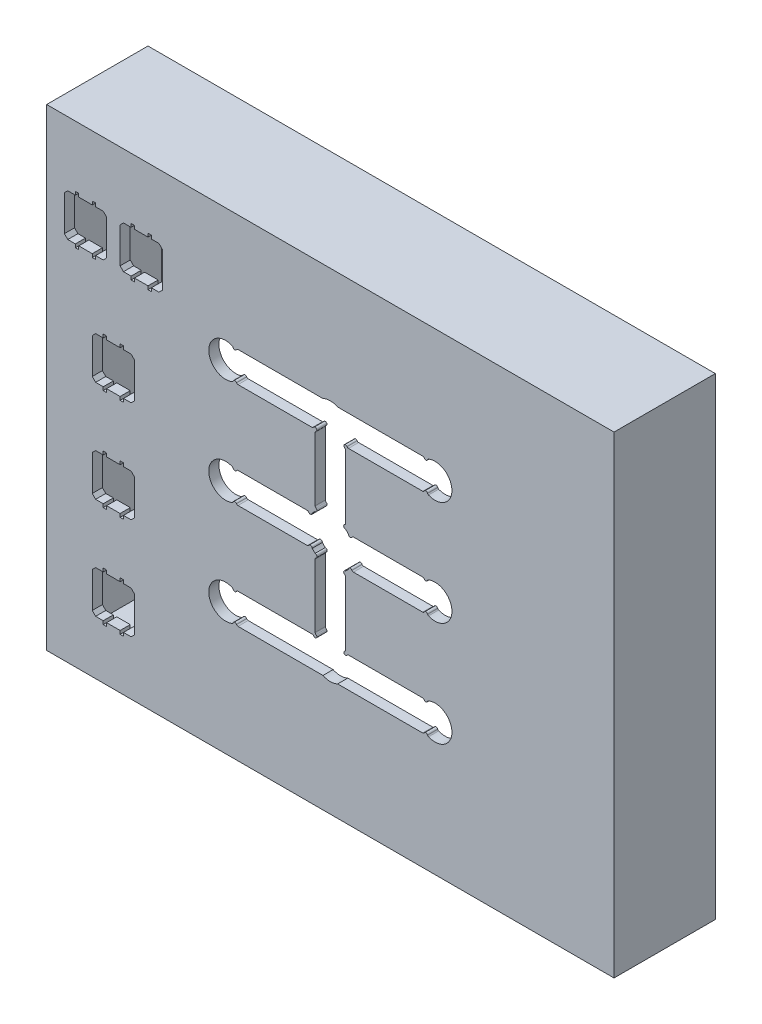
SolidWorks part; units mm, degrees
ref_plane "정면" through (0, 0, 0) normal (0, 0, 1) x (1, 0, 0)
ref_plane "윗면" through (0, 0, 0) normal (0, 1, 0) x (1, 0, 0)
ref_plane "우측면" through (0, 0, 0) normal (1, 0, 0) x (0, 0, -1)
sketch "스케치1" plane through (0, 0, 0) normal (0, 0, 1) x (1, 0, 0)
  line L1 (84, -70) -> (-84, -70)
  line L2 (84, -70) -> (84, 70)
  line L3 (84, 70) -> (-84, 70)
  line L4 (-84, -70) -> (-84, 70)
  line L5 (84, -70) -> (-84, 70) construction
  line L6 (84, 70) -> (-84, -70) construction
  point P0 (0, 0)
  dimension "D1" = 168
  dimension "D2" = 140
extrude "보스-돌출1" add sketch "스케치1" along normal blind 3
sketch "스케치3" plane through (0, 0, 0) normal (0, 0, -1) x (-1, 0, 0)
  line L1 (84, -70) -> (-84, -70)
  line L2 (84, -70) -> (84, 70)
  line L3 (84, 70) -> (-84, 70)
  line L4 (-84, -70) -> (-84, 70)
  line L5 (84, -70) -> (-84, 70) construction
  line L6 (84, 70) -> (-84, -70) construction
  point P0 (0, 0)
extrude "돌출-얇게3" add sketch "스케치3" along normal blind 27 thin
sketch "스케치11" plane through (0, 0, 3) normal (0, 0, 1) x (1, 0, 0)
  line L0 (58, 70) -> (58, -70) construction
  line L1 (84, 70) -> (-84, 70) construction
  line L2 (-84, -70) -> (84, -70) construction
  line L3 (84, -70) -> (84, 70) construction
  line L4 (64.25, -41.5) -> (64.25, -54) construction
  line L5 (58, -41.5) -> (70.5, -41.5)
  line L6 (58, -41.5) -> (58, -54)
  line L7 (58, -54) -> (70.5, -54)
  line L8 (70.5, -41.5) -> (70.5, -54)
  line L9 (61.25, -40.5) -> (62.25, -40.5)
  line L10 (61.25, -40.5) -> (61.25, -41.5)
  line L11 (61.25, -41.5) -> (62.25, -41.5)
  line L12 (62.25, -40.5) -> (62.25, -41.5)
  line L13 (64.25, -54) -> (64.25, -47.75) construction
  line L14 (64.25, -47.75) -> (70.5, -47.75) construction
  line L15 (67.25, -41.5) -> (66.25, -41.5)
  line L16 (66.25, -40.5) -> (66.25, -41.5)
  line L17 (67.25, -40.5) -> (66.25, -40.5)
  line L18 (67.25, -40.5) -> (67.25, -41.5)
  line L19 (61.25, -54) -> (62.25, -54)
  line L20 (62.25, -55) -> (62.25, -54)
  line L21 (61.25, -55) -> (62.25, -55)
  line L22 (61.25, -55) -> (61.25, -54)
  line L23 (67.25, -55) -> (67.25, -54)
  line L24 (67.25, -55) -> (66.25, -55)
  line L25 (66.25, -55) -> (66.25, -54)
  line L26 (67.25, -54) -> (66.25, -54)
  line L27 (64.25, -47.75) -> (64.25, 62.7587) construction
  line L28 (58, -11.5) -> (58, -24)
  line L29 (58, -11.5) -> (70.5, -11.5)
  line L30 (70.5, -11.5) -> (70.5, -24)
  line L31 (58, -24) -> (70.5, -24)
  line L32 (61.25, -10.5) -> (61.25, -11.5)
  line L33 (61.25, -10.5) -> (62.25, -10.5)
  line L34 (62.25, -10.5) -> (62.25, -11.5)
  line L35 (61.25, -11.5) -> (62.25, -11.5)
  line L36 (67.25, -11.5) -> (66.25, -11.5)
  line L37 (66.25, -10.5) -> (66.25, -11.5)
  line L38 (67.25, -10.5) -> (66.25, -10.5)
  line L39 (67.25, -10.5) -> (67.25, -11.5)
  line L40 (67.25, -25) -> (67.25, -24)
  line L41 (67.25, -24) -> (66.25, -24)
  line L42 (66.25, -25) -> (66.25, -24)
  line L43 (67.25, -25) -> (66.25, -25)
  line L44 (61.25, -24) -> (62.25, -24)
  line L45 (62.25, -25) -> (62.25, -24)
  line L46 (61.25, -25) -> (62.25, -25)
  line L47 (61.25, -25) -> (61.25, -24)
  line L48 (58, 18.5) -> (58, 6)
  line L49 (58, 18.5) -> (70.5, 18.5)
  line L50 (70.5, 18.5) -> (70.5, 6)
  line L51 (58, 6) -> (70.5, 6)
  line L52 (61.25, 19.5) -> (61.25, 18.5)
  line L53 (61.25, 19.5) -> (62.25, 19.5)
  line L54 (62.25, 19.5) -> (62.25, 18.5)
  line L55 (61.25, 18.5) -> (62.25, 18.5)
  line L56 (67.25, 18.5) -> (66.25, 18.5)
  line L57 (66.25, 19.5) -> (66.25, 18.5)
  line L58 (67.25, 19.5) -> (66.25, 19.5)
  line L59 (67.25, 19.5) -> (67.25, 18.5)
  line L60 (67.25, 5) -> (67.25, 6)
  line L61 (67.25, 6) -> (66.25, 6)
  line L62 (66.25, 5) -> (66.25, 6)
  line L63 (67.25, 5) -> (66.25, 5)
  line L64 (61.25, 6) -> (62.25, 6)
  line L65 (62.25, 5) -> (62.25, 6)
  line L66 (61.25, 5) -> (62.25, 5)
  line L67 (61.25, 5) -> (61.25, 6)
  line L68 (72.5, 51) -> (72.5, 38.5) construction
  line L69 (66.25, 51) -> (78.75, 51)
  line L70 (66.25, 51) -> (66.25, 38.5)
  line L71 (66.25, 38.5) -> (78.75, 38.5)
  line L72 (78.75, 51) -> (78.75, 38.5)
  line L73 (70.5, 52) -> (69.5, 52)
  line L74 (70.5, 52) -> (70.5, 51)
  line L75 (70.5, 51) -> (69.5, 51)
  line L76 (69.5, 52) -> (69.5, 51)
  line L77 (72.5, 38.5) -> (72.5, 44.75) construction
  line L78 (72.5, 44.75) -> (78.75, 44.75) construction
  line L79 (74.5, 51) -> (75.5, 51)
  line L80 (75.5, 52) -> (75.5, 51)
  line L81 (74.5, 52) -> (75.5, 52)
  line L82 (74.5, 52) -> (74.5, 51)
  line L83 (74.5, 37.5) -> (74.5, 38.5)
  line L84 (74.5, 37.5) -> (75.5, 37.5)
  line L85 (75.5, 37.5) -> (75.5, 38.5)
  line L86 (74.5, 38.5) -> (75.5, 38.5)
  line L87 (70.5, 38.5) -> (69.5, 38.5)
  line L88 (69.5, 37.5) -> (69.5, 38.5)
  line L89 (70.5, 37.5) -> (69.5, 37.5)
  line L90 (70.5, 37.5) -> (70.5, 38.5)
  line L91 (54, 37.5) -> (53, 37.5)
  line L92 (53, 37.5) -> (53, 38.5)
  line L93 (54, 38.5) -> (53, 38.5)
  line L94 (54, 37.5) -> (54, 38.5)
  line L95 (58, 37.5) -> (58, 38.5)
  line L96 (58, 37.5) -> (59, 37.5)
  line L97 (59, 37.5) -> (59, 38.5)
  line L98 (58, 38.5) -> (59, 38.5)
  line L99 (62.25, 38.5) -> (49.75, 38.5)
  line L100 (49.75, 51) -> (49.75, 38.5)
  line L101 (62.25, 51) -> (49.75, 51)
  line L102 (62.25, 51) -> (62.25, 38.5)
  line L103 (58, 51) -> (59, 51)
  line L104 (59, 52) -> (59, 51)
  line L105 (58, 52) -> (59, 52)
  line L106 (58, 52) -> (58, 51)
  line L107 (54, 52) -> (54, 51)
  line L108 (54, 52) -> (53, 52)
  line L109 (53, 52) -> (53, 51)
  line L110 (54, 51) -> (53, 51)
  line L111 (-58, -70) -> (-58, 70) construction
  line L112 (-84, 70) -> (-84, -70) construction
  line L113 (-64.25, -70) -> (-64.25, 70) construction
  line L114 (-64.25, -47.75) -> (-76.7581, -47.75) construction
  line L115 (-70.5, -41.5) -> (-58, -41.5)
  line L116 (-70.5, -41.5) -> (-70.5, -54)
  line L117 (-70.5, -54) -> (-58, -54)
  line L118 (-58, -41.5) -> (-58, -54)
  line L119 (-70.5, -41.5) -> (-58, -54) construction
  line L120 (-70.5, -54) -> (-58, -41.5) construction
  line L121 (-58, -24) -> (-70.5, -24)
  line L122 (-58, -24) -> (-58, -11.5)
  line L123 (-58, -11.5) -> (-70.5, -11.5)
  line L124 (-70.5, -24) -> (-70.5, -11.5)
  line L125 (-58, 6) -> (-70.5, 6)
  line L126 (-58, 6) -> (-58, 18.5)
  line L127 (-58, 18.5) -> (-70.5, 18.5)
  line L128 (-70.5, 6) -> (-70.5, 18.5)
  line L129 (-66.25, 38.5) -> (-78.75, 38.5)
  line L130 (-66.25, 38.5) -> (-66.25, 51)
  line L131 (-66.25, 51) -> (-78.75, 51)
  line L132 (-78.75, 38.5) -> (-78.75, 51)
  line L137 (-62.25, 38.5) -> (-49.75, 38.5)
  line L138 (-62.25, 38.5) -> (-62.25, 51)
  line L139 (-62.25, 51) -> (-49.75, 51)
  line L140 (-49.75, 38.5) -> (-49.75, 51)
  line L141 (-64.25, -17.75) -> (-76.7581, -17.75) construction
  line L142 (-64.25, 12.25) -> (-76.7581, 12.25) construction
  line L143 (-49.75, 44.75) -> (-78.75, 44.75) construction
  line L144 (-56, 38.5) -> (-56, 51) construction
  line L145 (-72.5, 38.5) -> (-72.5, 51) construction
  line L146 (-67.25, -54) -> (-66.25, -54)
  line L147 (-61.25, -55) -> (-62.25, -55)
  line L148 (-61.25, -55) -> (-61.25, -54)
  line L149 (-61.25, -54) -> (-62.25, -54)
  line L150 (-62.25, -55) -> (-62.25, -54)
  line L151 (-66.25, -55) -> (-66.25, -54)
  line L152 (-67.25, -55) -> (-66.25, -55)
  line L153 (-67.25, -55) -> (-67.25, -54)
  line L154 (-61.25, -41.5) -> (-62.25, -41.5)
  line L155 (-62.25, -40.5) -> (-62.25, -41.5)
  line L156 (-61.25, -40.5) -> (-62.25, -40.5)
  line L157 (-61.25, -40.5) -> (-61.25, -41.5)
  line L158 (-67.25, -40.5) -> (-67.25, -41.5)
  line L159 (-67.25, -40.5) -> (-66.25, -40.5)
  line L160 (-66.25, -40.5) -> (-66.25, -41.5)
  line L161 (-67.25, -41.5) -> (-66.25, -41.5)
  line L162 (-66.25, -11.5) -> (-67.25, -11.5)
  line L163 (-61.25, -25) -> (-62.25, -25)
  line L164 (-61.25, -25) -> (-61.25, -24)
  line L165 (-61.25, -24) -> (-62.25, -24)
  line L166 (-62.25, -25) -> (-62.25, -24)
  line L167 (-66.25, -25) -> (-67.25, -25)
  line L168 (-66.25, -25) -> (-66.25, -24)
  line L169 (-66.25, -24) -> (-67.25, -24)
  line L170 (-67.25, -25) -> (-67.25, -24)
  line L171 (-67.25, -10.5) -> (-67.25, -11.5)
  line L172 (-66.25, -10.5) -> (-67.25, -10.5)
  line L173 (-66.25, -10.5) -> (-66.25, -11.5)
  line L174 (-61.25, -11.5) -> (-62.25, -11.5)
  line L175 (-62.25, -10.5) -> (-62.25, -11.5)
  line L176 (-61.25, -10.5) -> (-62.25, -10.5)
  line L177 (-61.25, -10.5) -> (-61.25, -11.5)
  line L178 (-61.25, 18.5) -> (-62.25, 18.5)
  line L179 (-61.25, 5) -> (-62.25, 5)
  line L180 (-61.25, 5) -> (-61.25, 6)
  line L181 (-61.25, 6) -> (-62.25, 6)
  line L182 (-62.25, 5) -> (-62.25, 6)
  line L183 (-66.25, 5) -> (-67.25, 5)
  line L184 (-66.25, 5) -> (-66.25, 6)
  line L185 (-66.25, 6) -> (-67.25, 6)
  line L186 (-67.25, 5) -> (-67.25, 6)
  line L187 (-62.25, 19.5) -> (-62.25, 18.5)
  line L188 (-61.25, 19.5) -> (-62.25, 19.5)
  line L189 (-61.25, 19.5) -> (-61.25, 18.5)
  line L190 (-66.25, 18.5) -> (-67.25, 18.5)
  line L191 (-67.25, 19.5) -> (-67.25, 18.5)
  line L192 (-66.25, 19.5) -> (-67.25, 19.5)
  line L193 (-66.25, 19.5) -> (-66.25, 18.5)
  line L194 (-59, 38.5) -> (-58, 38.5)
  line L195 (-53, 37.5) -> (-54, 37.5)
  line L196 (-53, 37.5) -> (-53, 38.5)
  line L197 (-53, 38.5) -> (-54, 38.5)
  line L198 (-54, 37.5) -> (-54, 38.5)
  line L199 (-70.5, 38.5) -> (-69.5, 38.5)
  line L200 (-70.5, 38.5) -> (-70.5, 37.5)
  line L201 (-70.5, 37.5) -> (-69.5, 37.5)
  line L202 (-69.5, 38.5) -> (-69.5, 37.5)
  line L203 (-58, 37.5) -> (-58, 38.5)
  line L204 (-59, 37.5) -> (-58, 37.5)
  line L205 (-59, 37.5) -> (-59, 38.5)
  line L206 (-59, 52) -> (-59, 51)
  line L207 (-59, 52) -> (-58, 52)
  line L208 (-58, 52) -> (-58, 51)
  line L209 (-59, 51) -> (-58, 51)
  line L210 (-53, 51) -> (-54, 51)
  line L211 (-54, 52) -> (-54, 51)
  line L212 (-53, 52) -> (-54, 52)
  line L213 (-53, 52) -> (-53, 51)
  line L214 (-74.5, 37.5) -> (-75.5, 37.5)
  line L215 (-75.5, 38.5) -> (-75.5, 37.5)
  line L216 (-74.5, 38.5) -> (-75.5, 38.5)
  line L217 (-74.5, 38.5) -> (-74.5, 37.5)
  line L218 (-74.5, 51) -> (-74.5, 52)
  line L219 (-74.5, 51) -> (-75.5, 51)
  line L220 (-75.5, 51) -> (-75.5, 52)
  line L221 (-74.5, 52) -> (-75.5, 52)
  line L222 (-70.5, 52) -> (-69.5, 52)
  line L223 (-69.5, 51) -> (-69.5, 52)
  line L224 (-70.5, 51) -> (-69.5, 51)
  line L225 (-70.5, 51) -> (-70.5, 52)
  point P24 (62.25, -41)
  point P90 (74.5, 51.5)
  point P125 (-64.25, -47.75)
  point P210 (-54, 38)
  point P215 (-70.5, 38)
  dimension "D1" = 26
  dimension "D2" = 12.5
  dimension "D3" = 12.5
  dimension "D4" = 1
  dimension "D5" = 1
  dimension "D6" = 4
  dimension "D7" = 16
  dimension "D9" = 12.5
  dimension "D10" = 12.5
  dimension "D11" = 1
  dimension "D12" = 1
  dimension "D13" = 4
  dimension "D14" = 2
  dimension "D15" = 19
  dimension "D16" = 26
  dimension "D17" = 6.25
  dimension "D18" = 12.5
  dimension "D19" = 12.5
  dimension "D20" = 2
  dimension "D21" = 2
  dimension "D22" = 1
  dimension "D23" = 2
  dimension "D24" = 2
  dimension "D25" = 1
  dimension "D26" = 1
  dimension "D27" = 2
  dimension "D8" = 3
extrude "컷-돌출3" cut sketch "스케치11" against normal blind 27 contours L118 L115 L116 L117 | L153 L152 L151 L117 | L150 L147 L148 L117 | L124 L121 L122 L123 | L166 L163 L164 L121 | L170 L167 L168 L121 | L173 L172 L171 L123 | L177 L176 L175 L123 | L128 L125 L126 L127 | L189 L188 L187 L127 | L193 L192 L191 L127 | L186 L183 L184 L125 | L182 L179 L180 L125 | L137 L140 L139 L138 | L205 L204 L203 L137 | L213 L212 L211 L139 | L208 L207 L206 L139 | L132 L129 L130 L131 | L217 L129 L215 L214 | L202 L129 L200 L201 | L225 L131 L223 L222 | L218 L221 L220 L131 | L160 L161 L158 L159 | L157 L154 L155 L156 | L195 L198 L197 L196
sketch "스케치19" plane through (0, 66, 0) normal (0, -1, 0) x (1, 0, 0)
  line L0 (-80, 0) -> (80, 0) construction
  line L1 (-45, -23.5) -> (45, -23.5)
  line L2 (-45, -23.5) -> (-45, -25.5)
  line L3 (-45, -25.5) -> (45, -25.5)
  line L4 (45, -23.5) -> (45, -25.5)
  line L5 (-45, -23.5) -> (45, -25.5) construction
  line L6 (-45, -25.5) -> (45, -23.5) construction
  line L9 (-80, -27) -> (80, -27) construction
  point P0 (0, -24.5)
  point P7 (0, 0)
  dimension "D1" = 90
  dimension "D2" = 0
  dimension "D3" = 2
  dimension "D4" = 2.5
extrude "컷-돌출6" cut sketch "스케치19" against normal blind 1
sketch "스케치20" plane through (0, -66, 0) normal (0, 1, 0) x (1, 0, 0)
  line L0 (80, 27) -> (-80, 27) construction
  line L1 (-45, 23.5) -> (45, 23.5)
  line L2 (-45, 23.5) -> (-45, 25.5)
  line L3 (-45, 25.5) -> (45, 25.5)
  line L4 (45, 23.5) -> (45, 25.5)
  line L5 (-45, 23.5) -> (45, 25.5) construction
  line L6 (-45, 25.5) -> (45, 23.5) construction
  point P0 (0, 24.5)
  dimension "D1" = 2.5
  dimension "D2" = 2
  dimension "D3" = 90
extrude "컷-돌출7" cut sketch "스케치20" against normal blind 1
sketch "스케치22" plane through (0, 0, 3) normal (0, 0, 1) x (1, 0, 0)
  line L0 (0, 0) -> (0, 46.9724) construction
  line L1 (0, 46.9724) -> (0, 0) construction
  line L2 (0, 0) -> (50.8786, 0) construction
  line L3 (84, 70) -> (-84, 70) construction
  line L4 (-84, 70) -> (-84, -70) construction
  line L6 (-31, -4.5) -> (31, -4.5)
  line L7 (-31, -4.5) -> (-31, 4.5)
  line L8 (-31, 4.5) -> (31, 4.5)
  line L9 (31, -4.5) -> (31, 4.5)
  line L10 (-31, -4.5) -> (31, 4.5) construction
  line L11 (-31, 4.5) -> (31, -4.5) construction
  line L12 (-31, 35.5) -> (31, 35.5)
  line L13 (-31, 35.5) -> (-31, 26.5)
  line L14 (-31, 26.5) -> (31, 26.5)
  line L15 (31, 35.5) -> (31, 26.5)
  line L16 (-31, 35.5) -> (31, 26.5) construction
  line L17 (-31, 26.5) -> (31, 35.5) construction
  line L18 (-31, -35.5) -> (31, -35.5)
  line L19 (-31, -35.5) -> (-31, -26.5)
  line L20 (-31, -26.5) -> (31, -26.5)
  line L21 (31, -35.5) -> (31, -26.5)
  line L22 (-31, -35.5) -> (31, -26.5) construction
  line L23 (-31, -26.5) -> (31, -35.5) construction
  line L24 (-4.5, 31) -> (4.5, 31)
  line L25 (-4.5, 31) -> (-4.5, -31)
  line L26 (-4.5, -31) -> (4.5, -31)
  line L27 (4.5, 31) -> (4.5, -31)
  line L28 (-4.5, 31) -> (4.5, -31) construction
  line L29 (-4.5, -31) -> (4.5, 31) construction
  circle A0 centre (-31, 31) radius 5
  circle A1 centre (31, 31) radius 5
  circle A2 centre (0, 31) radius 5
  circle A3 centre (0, 0) radius 7
  circle A4 centre (-31, 0) radius 5
  circle A5 centre (31, 0) radius 5
  circle A6 centre (31, -31) radius 5
  circle A7 centre (0, -31) radius 5
  circle A8 centre (-31, -31) radius 5
  dimension "D3" = 10
  dimension "D4" = 10
  dimension "D5" = 14
  dimension "D6" = 9
  dimension "D1" = 39
  dimension "D2" = 53
  dimension "D7" = 9
  dimension "D8" = 9
  dimension "D9" = 9
extrude "컷-돌출10" cut sketch "스케치22" against normal blind 10 contours A0 | A2 | A1 | A5 | A3 | A4 | A8 | A7 | A6 | L20 L21 L18 L19 | L6 L9 L8 L7 | L14 L15 L12 L13 | L27 L26 L25 L24
sketch "스케치24" plane through (0, 0, 0) normal (0, 0, -1) x (-1, 0, 0)
  line L0 (28.8206, 35.5) -> (2.1794, 35.5) construction
  line L1 (28.8206, 26.5) -> (4.5, 26.5) construction
  line L2 (-2.1794, 35.5) -> (-28.8206, 35.5) construction
  line L3 (-4.5, 26.5) -> (-28.8206, 26.5) construction
  line L4 (28.8206, 4.5) -> (5.3619, 4.5) construction
  line L5 (28.8206, -4.5) -> (5.3619, -4.5) construction
  line L6 (-5.3619, 4.5) -> (-28.8206, 4.5) construction
  line L7 (-5.3619, -4.5) -> (-28.8206, -4.5) construction
  line L8 (-4.5, -26.5) -> (-28.8206, -26.5) construction
  line L9 (-2.1794, -35.5) -> (-28.8206, -35.5) construction
  line L10 (28.8206, -26.5) -> (4.5, -26.5) construction
  line L11 (28.8206, -35.5) -> (2.1794, -35.5) construction
  line L12 (4.5, -5.3619) -> (4.5, -26.5) construction
  line L13 (-4.5, -5.3619) -> (-4.5, -26.5) construction
  line L14 (4.5, 26.5) -> (4.5, 5.3619) construction
  line L15 (-4.5, 26.5) -> (-4.5, 5.3619) construction
  circle A0 centre (28.2706, 35.5) radius 0.55
  circle A1 centre (28.2706, 26.5) radius 0.55
  circle A2 centre (-28.2706, 35.5) radius 0.55
  circle A3 centre (-28.2706, 26.5) radius 0.55
  circle A4 centre (28.2706, 4.5) radius 0.55
  circle A5 centre (28.2706, -4.5) radius 0.55
  circle A6 centre (-28.2706, 4.5) radius 0.55
  circle A7 centre (-28.2706, -4.5) radius 0.55
  circle A8 centre (-28.2706, -26.5) radius 0.55
  circle A9 centre (-28.2706, -35.5) radius 0.55
  circle A10 centre (28.2706, -26.5) radius 0.55
  circle A11 centre (28.2706, -35.5) radius 0.55
  circle A12 centre (5.9119, 4.5) radius 0.55
  circle A13 centre (5.9119, -4.5) radius 0.55
  circle A14 centre (4.5, -5.9119) radius 0.55
  circle A15 centre (-4.5, -5.9119) radius 0.55
  circle A16 centre (-5.9119, -4.5) radius 0.55
  circle A17 centre (-5.9119, 4.5) radius 0.55
  circle A18 centre (4.5, 5.9119) radius 0.55
  circle A19 centre (-4.5, 5.9119) radius 0.55
  circle A20 centre (-4.5, -26.5) radius 0.5
  circle A21 centre (4.5, -26.5) radius 0.5
  circle A22 centre (4.5, 26.5) radius 0.5
  circle A23 centre (-4.5, 26.5) radius 0.5
  dimension "D1" = 1.1
  dimension "D2" = 0.55
  dimension "D3" = 1.1
  dimension "D4" = 1.1
  dimension "D5" = 1.1
  dimension "D6" = 1.1
  dimension "D8" = 1.1
  dimension "D10" = 1.1
  dimension "D11" = 1.1
  dimension "D12" = 1.1
  dimension "D13" = 1.1
  dimension "D14" = 1.1
  dimension "D7" = 0.55
  dimension "D9" = 0.55
extrude "보스-돌출2" add sketch "스케치24" against normal blind 3
fillet "필렛1" radius 0.5 28 edges at (-4.5, 6.4619, 1.5) (-27.7206, -35.5, 1.5) (27.7206, -35.5, 1.5) (27.7206, -26.5, 1.5) (5, -26.5, 1.5) (4.5, -26, 1.5) (-4.5, -26, 1.5) (-5, -26.5, 1.5) (-27.7206, -26.5, 1.5) (-4.5, -6.4619, 1.5) (4.5, -6.4619, 1.5) (6.4619, -4.5, 1.5) (6.4619, 4.5, 1.5) (4.5, 6.4619, 1.5) (27.7206, -4.5, 1.5) (27.7206, 4.5, 1.5) (27.7206, 35.5, 1.5) (27.7206, 26.5, 1.5) (5, 26.5, 1.5) (4.5, 26, 1.5) (-4.5, 26, 1.5) (-5, 26.5, 1.5) (-27.7206, 26.5, 1.5) (-27.7206, 35.5, 1.5) (-27.7206, -4.5, 1.5) (-27.7206, 4.5, 1.5) (-6.4619, -4.5, 1.5) (-6.4619, 4.5, 1.5)
fillet "필렛2" radius 0.5 12 edges at (28.8206, -4.5, 1.5) (28.8206, 4.5, 1.5) (28.8206, -35.5, 1.5) (28.8206, -26.5, 1.5) (-28.8206, -35.5, 1.5) (-28.8206, -26.5, 1.5) (-28.8206, -4.5, 1.5) (-28.8206, 4.5, 1.5) (28.8206, 35.5, 1.5) (28.8206, 26.5, 1.5) (-28.8206, 26.5, 1.5) (-28.8206, 35.5, 1.5)
chamfer "모따기1" distance 1 angle 45 20 edges at (-58, -54, 1.5) (-70.5, -54, 1.5) (-58, -41.5, 1.5) (-70.5, -41.5, 1.5) (-70.5, -24, 1.5) (-70.5, -11.5, 1.5) (-58, -11.5, 1.5) (-58, -24, 1.5) (-70.5, 6, 1.5) (-70.5, 18.5, 1.5) (-58, 18.5, 1.5) (-58, 6, 1.5) (-78.75, 38.5, 1.5) (-78.75, 51, 1.5) (-66.25, 51, 1.5) (-66.25, 38.5, 1.5) (-62.25, 38.5, 1.5) (-62.25, 51, 1.5) (-49.75, 51, 1.5) (-49.75, 38.5, 1.5)
